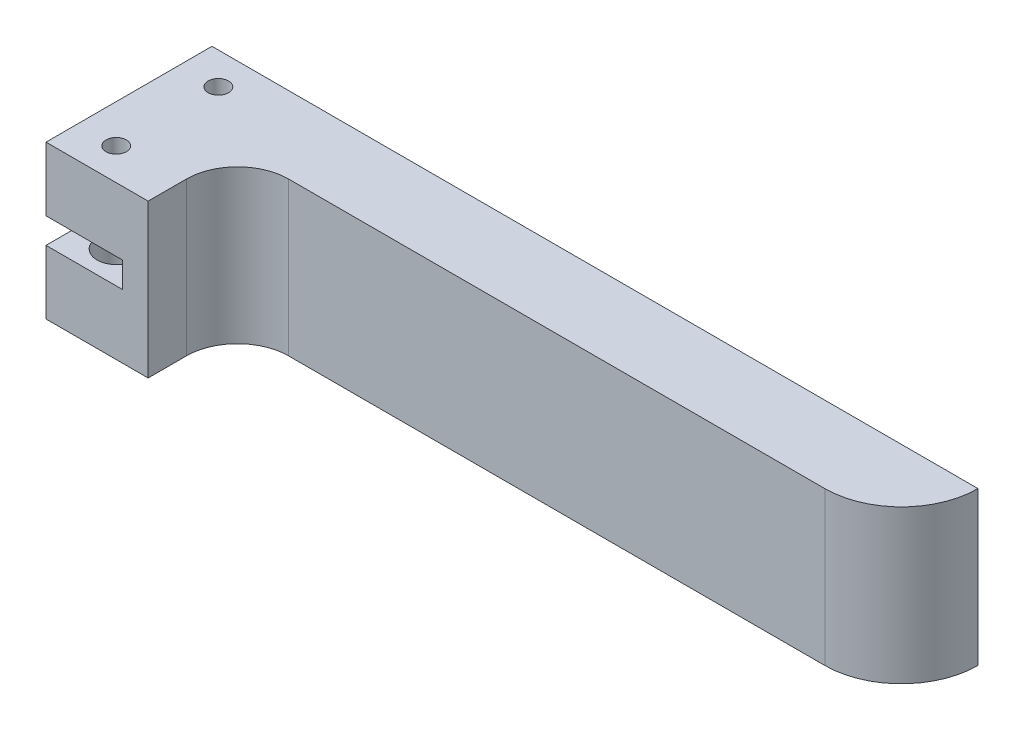
SolidWorks part; units mm, degrees
ref_plane "Front Plane" through (0, 0, 0) normal (0, 0, 1) x (1, 0, 0)
ref_plane "Top Plane" through (0, 0, 0) normal (0, 1, 0) x (1, 0, 0)
ref_plane "Right Plane" through (0, 0, 0) normal (1, 0, 0) x (0, 0, -1)
sketch "Sketch1" plane through (0, 0, 0) normal (0, 1, 0) x (1, 0, 0)
  line L1 (20, -6.5) -> (-20, -6.5)
  line L2 (20, -6.5) -> (20, 6.5)
  line L3 (20, 6.5) -> (-20, 6.5)
  line L4 (-20, -6.5) -> (-20, 6.5)
  line L5 (20, -6.5) -> (-20, 6.5) construction
  line L6 (20, 6.5) -> (-20, -6.5) construction
  point P0 (0, 0)
  dimension "D1" = 13
  dimension "D2" = 40
extrude "Boss-Extrude1" add sketch "Sketch1" along normal blind 6
sketch "Sketch2" plane through (0, 0, 6.5) normal (0, 0, 1) x (1, 0, 0)
  line L0 (-20, 6) -> (-20, 0) construction
  line L1 (-20, 4) -> (-14, 4)
  line L2 (-20, 4) -> (-20, 2)
  line L3 (-20, 2) -> (-14, 2)
  line L4 (-14, 4) -> (-14, 2)
  line L5 (-20, 0) -> (20, 0) construction
  point P6 (-20, 3)
  dimension "D1" = 2
  dimension "D2" = 6
  dimension "D3" = 3
extrude "Cut-Extrude1" cut sketch "Sketch2" against normal through all
sketch "Sketch3" plane through (0, 6, 0) normal (0, 1, 0) x (1, 0, 0)
  line L0 (-20, 6.5) -> (-20, -6.5) construction
  line L1 (20, 6.5) -> (-20, 6.5) construction
  circle A0 centre (-17, 4) radius 0.8
  circle A1 centre (-17, -4) radius 0.8
  dimension "D1" = 1.6
  dimension "D3" = 2.5
  dimension "D4" = 1.6
  dimension "D5" = 8
  dimension "D2" = 3
extrude "Cut-Extrude2" cut sketch "Sketch3" against normal blind 2
sketch "Sketch4" plane through (0, 6, 0) normal (0, 1, 0) x (1, 0, 0)
  line L1 (20, -6.5) -> (-12, -6.5)
  line L2 (20, -6.5) -> (20, 0.5)
  line L3 (20, 0.5) -> (-12, 0.5)
  line L4 (-12, -6.5) -> (-12, 0.5)
  dimension "D1" = 32
  dimension "D2" = 7
extrude "Cut-Extrude3" cut sketch "Sketch4" against normal through all
fillet "Fillet1" radius 4 1 edges at (-12, 3, -0.5)
sketch "Sketch5" plane through (0, 2, 0) normal (0, 1, 0) x (1, 0, 0)
  circle A0 centre (-17, 4) radius 1.5
  circle A1 centre (-17, -4) radius 1.5
  dimension "D1" = 3
  dimension "D2" = 3
extrude "Cut-Extrude4" cut sketch "Sketch5" against normal blind 2
sketch "Sketch6" plane through (20, 0, 0) normal (1, 0, 0) x (0, 0, -1)
  line L4 (6.5, 6) -> (0.5, 6)
  line L5 (0.5, 6) -> (0.5, 0)
  line L6 (0.5, 0) -> (6.5, 0)
  line L7 (6.5, 0) -> (6.5, 6)
  line L8 (6.5, 6) -> (0.5, 6)
  line L9 (0.5, 6) -> (0.5, 0)
  line L10 (0.5, 0) -> (6.5, 0)
  line L11 (6.5, 0) -> (6.5, 6)
  dimension "D1" = 0
extrude "Boss-Extrude2" add sketch "Sketch6" along normal blind 20
fillet "Fillet3" radius 6 1 edges at (40, 3, -0.5)
sketch "Sketch7" plane through (0, 0, 0) normal (0, -1, 0) x (1, 0, 0)
  line L5 (-20, -6.5) -> (40, -6.5)
  line L6 (34, -0.5) -> (-8, -0.5)
  line L7 (-12, 3.5) -> (-12, 6.5)
  line L8 (-12, 6.5) -> (-20, 6.5)
  line L9 (-20, 6.5) -> (-20, -6.5)
  line L10 (-20, -6.5) -> (40, -6.5)
  line L11 (34, -0.5) -> (-8, -0.5)
  line L12 (-12, 3.5) -> (-12, 6.5)
  line L13 (-12, 6.5) -> (-20, 6.5)
  line L14 (-20, 6.5) -> (-20, -6.5)
  circle A0 centre (-17, 4) radius 1.5 construction
  circle A1 centre (-17, 4) radius 1.5
  arc A2 (40, -6.5) -> (34, -0.5) centre (34, -6.5) ccw
  arc A3 (-12, 3.5) -> (-8, -0.5) centre (-8, 3.5) ccw
  arc A4 (40, -6.5) -> (34, -0.5) centre (34, -6.5) ccw
  arc A5 (-12, 3.5) -> (-8, -0.5) centre (-8, 3.5) ccw
  circle A6 centre (-17, -4) radius 1.5 construction
  circle A7 centre (-17, -4) radius 1.5
  dimension "D1" = 0
extrude "Boss-Extrude3" add sketch "Sketch7" along normal blind 3
sketch "Sketch8" plane through (0, 6, 0) normal (0, 1, 0) x (1, 0, 0)
  line L5 (-8, 0.5) -> (34, 0.5)
  line L6 (40, 6.5) -> (-20, 6.5)
  line L7 (-20, 6.5) -> (-20, -6.5)
  line L8 (-20, -6.5) -> (-12, -6.5)
  line L9 (-12, -6.5) -> (-12, -3.5)
  line L10 (-8, 0.5) -> (34, 0.5)
  line L11 (40, 6.5) -> (-20, 6.5)
  line L12 (-20, 6.5) -> (-20, -6.5)
  line L13 (-20, -6.5) -> (-12, -6.5)
  line L14 (-12, -6.5) -> (-12, -3.5)
  circle A0 centre (-17, -4) radius 0.8 construction
  circle A1 centre (-17, -4) radius 0.8
  arc A2 (34, 0.5) -> (40, 6.5) centre (34, 6.5) ccw
  arc A3 (-8, 0.5) -> (-12, -3.5) centre (-8, -3.5) ccw
  arc A4 (34, 0.5) -> (40, 6.5) centre (34, 6.5) ccw
  arc A5 (-8, 0.5) -> (-12, -3.5) centre (-8, -3.5) ccw
  circle A6 centre (-17, 4) radius 0.8 construction
  circle A7 centre (-17, 4) radius 0.8
  dimension "D1" = 0
extrude "Boss-Extrude4" add sketch "Sketch8" along normal blind 3
